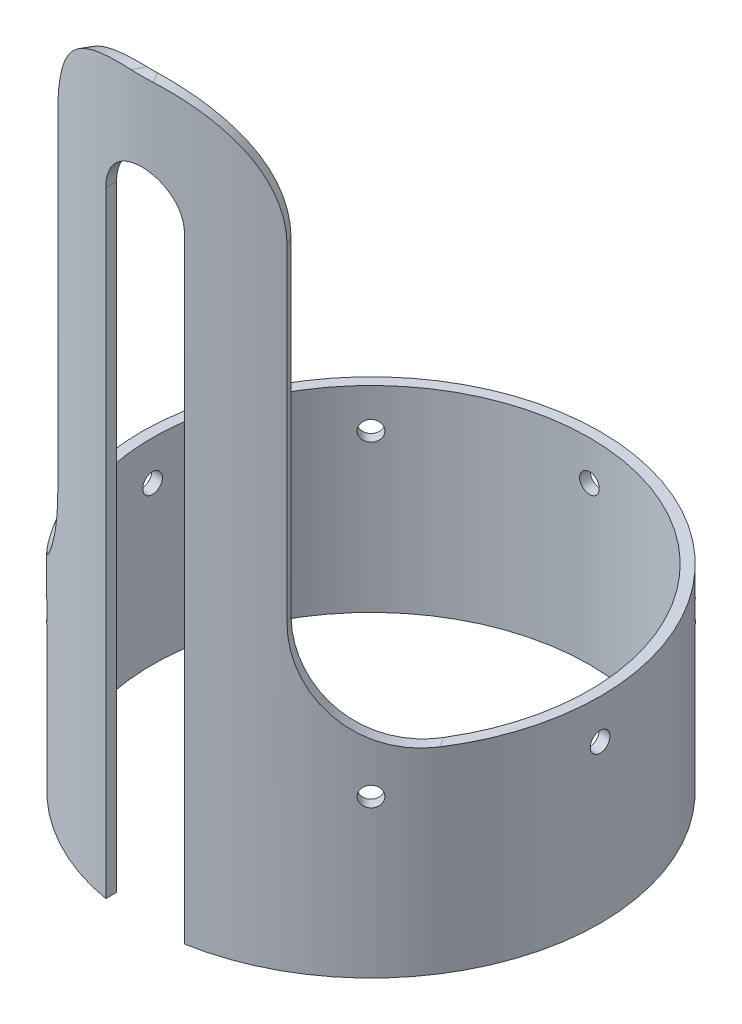
SolidWorks part; units mm, degrees
material "ABS"
ref_plane "Front Plane" through (0, 0, 0) normal (0, 0, 1) x (1, 0, 0)
ref_plane "Top Plane" through (0, 0, 0) normal (0, 1, 0) x (1, 0, 0)
ref_plane "Right Plane" through (0, 0, 0) normal (1, 0, 0) x (0, 0, -1)
sketch "Sketch1" plane through (0, 0, 0) normal (0, 1, 0) x (1, 0, 0)
  circle A0 centre (0, 0) radius 55.5625
  circle A1 centre (0, 0) radius 52.9844
  dimension "D1" = 111.125
  dimension "D2" = 105.9688
extrude "Boss-Extrude1" add sketch "Sketch1" along normal blind 177.8
sketch "Sketch2" plane through (0, 0, 0) normal (0, 0, 1) x (1, 0, 0)
  line L0 (0, 158.75) -> (0, 0) construction
  line L1 (-9.525, 149.225) -> (-9.525, 0)
  line L2 (-55.5625, 0) -> (55.5625, 0) construction
  line L3 (9.525, 149.225) -> (9.525, 0)
  line L4 (9.525, 0) -> (-9.525, 0)
  arc A0 (9.525, 149.225) -> (-9.525, 149.225) centre (0, 149.225) ccw
  dimension "D2" = 19.05
  dimension "D1" = 158.75
extrude "Cut-Extrude1" cut sketch "Sketch2" along normal through all
ref_plane "Plane1" through (0, 0, -55.5625) normal (0, 0, -1) x (-1, 0, 0)
hole_wizard "3/16 (0.1875) Diameter Hole1" positions "Sketch3" profile "Sketch4" hole size "3/16" standard "ANSI Inch"
sketch "Sketch3" plane through (0, 0, -55.5625) normal (0, 0, -1) x (-1, 0, 0)
  point P0 (0, 38.1)
  dimension "D1" = 38.1
sketch "Sketch4" plane through (0, 38.1, -55.5625) normal (1, 0, 0) x (0, 1, 0)
  line L0 (0, 0) -> (0, 12.0988)
  line L1 (0, 12.0988) -> (2.3812, 10.668)
  line L2 (2.3812, 10.668) -> (2.3812, 0)
  line L5 (2.3812, 0) -> (0, 0)
  line L10 (0, 12.0988) -> (-2.3813, 10.668) construction
  line L11 (0, -6.35) -> (0, 107.95) construction
  dimension "Hole Dia." = 4.7625
  dimension "Hole Depth" = 10.668
  dimension "Drill Angle" = 118
pattern_circular "CirPattern1" count 8 over 360 about axis through (0, 177.8, 0) along (0, -1, 0) skipping 4 of "3/16 (0.1875) Diameter Hole1" reverse direction yes
sketch "Sketch5" plane through (0, 0, 0) normal (0, 0, 1) x (1, 0, 0)
  line L0 (0, 0) -> (0, 196.9609) construction
  line L1 (50.8, 200.025) -> (63.5, 200.025)
  line L2 (50.8, 200.025) -> (50.8, 47.625)
  line L3 (50.8, 47.625) -> (63.5, 47.625)
  line L4 (63.5, 200.025) -> (63.5, 47.625)
  line L5 (-55.5625, 0) -> (55.5625, 0) construction
  dimension "D1" = 47.625
  dimension "D2" = 50.8
  dimension "D3" = 12.7
  dimension "D4" = 152.4
revolve "Cut-Revolve1" cut sketch "Sketch5" angle 240 about L0 other way angle 60
fillet "Fillet1" radius 25.4 4 edges at (27.1367, 177.8, 47.0022) (-27.1367, 177.8, 47.0022) (-27.1367, 47.625, 47.0022) (27.1367, 47.625, 47.0022)
